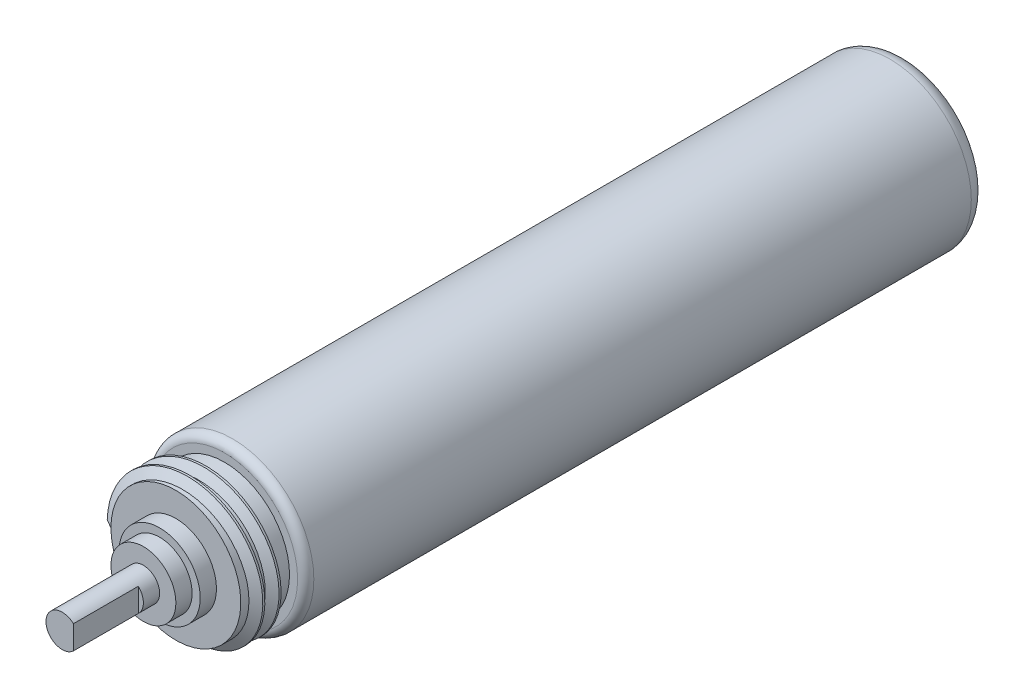
SolidWorks part; units mm, degrees
ref_plane "Front Plane" through (0, 0, 0) normal (0, 0, 1) x (1, 0, 0)
ref_plane "Top Plane" through (0, 0, 0) normal (0, 1, 0) x (1, 0, 0)
ref_plane "Right Plane" through (0, 0, 0) normal (1, 0, 0) x (0, 0, -1)
other "Configuration Table"
sketch "Sketch1" plane through (0, 0, 0) normal (0, 0, 1) x (1, 0, 0)
  circle A0 centre (0, 0) radius 5
  dimension "D1" = 10
extrude "Boss-Extrude1" add sketch "Sketch1" along normal blind 42
fillet "Fillet1" radius 1 1 edges at (5, 0, 0)
fillet "Fillet2" radius 0.5 1 edges at (5, 0, 42)
sketch "Sketch2" plane through (0, 0, 42) normal (0, 0, 1) x (1, 0, 0)
  circle A0 centre (0, 0) radius 4
  dimension "D1" = 8
extrude "Boss-Extrude2" add sketch "Sketch2" along normal blind 3
sketch "Sketch3" plane through (0, 0, 45) normal (0, 0, 1) x (1, 0, 0)
  circle A0 centre (0, 0) radius 2.5
  dimension "D1" = 5
extrude "Boss-Extrude3" add sketch "Sketch3" along normal blind 1
sketch "Sketch4" plane through (0, 0, 46) normal (0, 0, 1) x (1, 0, 0)
  circle A0 centre (0, 0) radius 2
  dimension "D1" = 4
extrude "Boss-Extrude4" add sketch "Sketch4" along normal blind 1
sketch "Sketch5" plane through (0, 0, 47) normal (0, 0, 1) x (1, 0, 0)
  circle A0 centre (0, 0) radius 1
  dimension "D1" = 2
extrude "Boss-Extrude5" add sketch "Sketch5" along normal blind 5
thread "Thread1" pitch 1 method extrude profile "Thread Profile1" start angle 0, offset 0, length 2, pitch 1, diameter 8
ref_plane "Plane1" through (-4, 0, 45) normal (0, -1, 0) x (-1, 0, 0)
sketch "Thread Profile1" plane through (-4, 0, 45) normal (0, -1, 0) x (-1, 0, 0)
  line L0 (0, 0) -> (0, 1) construction
  line L1 (0, 0) -> (0.5413, 0.3125)
  line L2 (0.5413, 0.3125) -> (0.5413, 0.4375)
  line L3 (0.5413, 0.4375) -> (0, 0.75)
  line L4 (0.5413, 0.375) -> (0, 0.375) construction
  line L11 (0, 0) -> (0, 0.75)
  point P2 (0, 0)
  dimension "Pitch" = 1
  dimension "Profile_Angle" = 60
  dimension "Profile_Land" = 0.125
  dimension "Profile_Height" = 0.5413
sketch "Sketch8" plane through (0, 0, 52) normal (0, 0, 1) x (1, 0, 0)
  line L0 (0.6876, 0.726) -> (0.6876, -0.726)
  circle A0 centre (0, 0) radius 1 construction
  circle A1 centre (0, 0) radius 1
  circle M1 centre (0, 0) radius 1
extrude "Cut-Extrude1" cut sketch "Sketch8" against normal blind 4 contours L0 M1 region at (0.8144, 0, 52)
